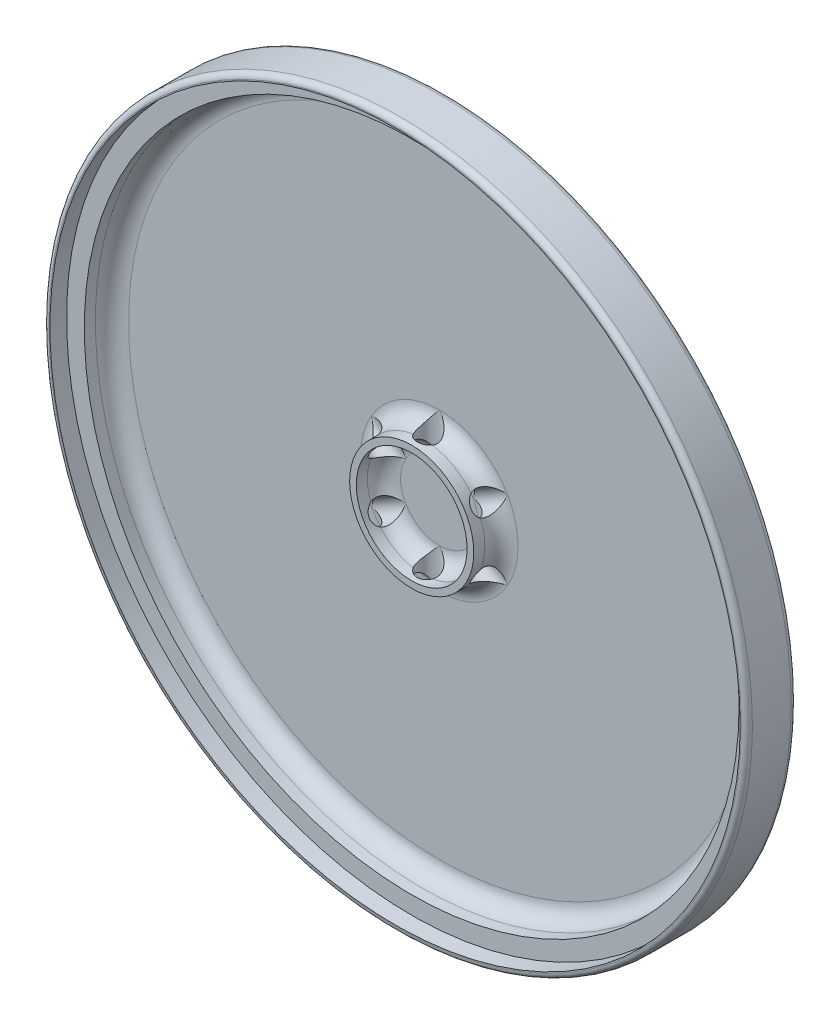
SolidWorks part; units mm, degrees
note: The reader was unsure of these and kept them because the rebuilt part matched: shared geometry of "Sketch1<3>", "Sketch1<4>", "Sketch1<5>".
ref_plane "Front Plane" through (0, 0, 0) normal (0, 0, 1) x (1, 0, 0)
ref_plane "Top Plane" through (0, 0, 0) normal (0, 1, 0) x (1, 0, 0)
ref_plane "Right Plane" through (0, 0, 0) normal (1, 0, 0) x (0, 0, -1)
sketch "Sketch1" plane through (0, 0, 0) normal (0, 0, 1) x (1, 0, 0)
  circle A0 centre (0, 0) radius 63.5
  circle A1 centre (0, 0) radius 62.3
  circle A2 centre (0, 0) radius 59.1
  circle A3 centre (0, 0) radius 10
  circle A4 centre (0, 0) radius 11.2
  dimension "D1" = 127
  dimension "D5" = 20
  dimension "D2" = 1.2
  dimension "D3" = 3.2
  dimension "D4" = 1.2
extrude "Boss-Extrude1" add sketch "Sketch1" against normal blind 1 contours A2 A4 | A1 A2 | A0 A1 | A3 | A4 A3
extrude "Boss-Extrude2" add sketch "Sketch1<3>" along normal blind 8 contours A0 A1
sketch "Sketch1<3>" plane through (0, 0, 0) normal (0, 0, 1) x (1, 0, 0) same geometry as "Sketch1"
extrude "Boss-Extrude3" add sketch "Sketch1<4>" along normal blind 5 contours A1 A2
sketch "Sketch1<4>" plane through (0, 0, 0) normal (0, 0, 1) x (1, 0, 0) same geometry as "Sketch1"
extrude "Boss-Extrude4" add sketch "Sketch1<5>" along normal blind 5 contours A4 A3
sketch "Sketch1<5>" plane through (0, 0, 0) normal (0, 0, 1) x (1, 0, 0) same geometry as "Sketch1"
sketch "Sketch2" plane through (0, 0, 0) normal (0, 1, 0) x (1, 0, 0)
  line L2 (-10, 0) -> (10, 0) construction
  circle A0 centre (0, -2) radius 2
  dimension "D1" = 4
extrude "Cut-Extrude3" cut sketch "Sketch2" against normal up to next and the other way up to next
fillet "Fillet1" radius 3 1 edges at (59.1, 0, 0)
fillet "Fillet2" radius 3 8 edges at (10, 0, 0) (-11.2, 0, 0) (-0.4244, 11.192, 3.9544) (-0.4155, 9.9914, 3.9564) (-10, 0, 0) (11.2, 0, 0) (0, -11.2, 4) (0, -10, 4)
fillet "Fillet3" radius 1 1 edges at (63.5, 0, -1)
fillet "Fillet4" radius 1 1 edges at (63.5, 0, 8)
pattern_circular "CirPattern1" count 3 over 360 about axis through (0, 0, 5) along (0, 0, -1) of "Cut-Extrude3"
